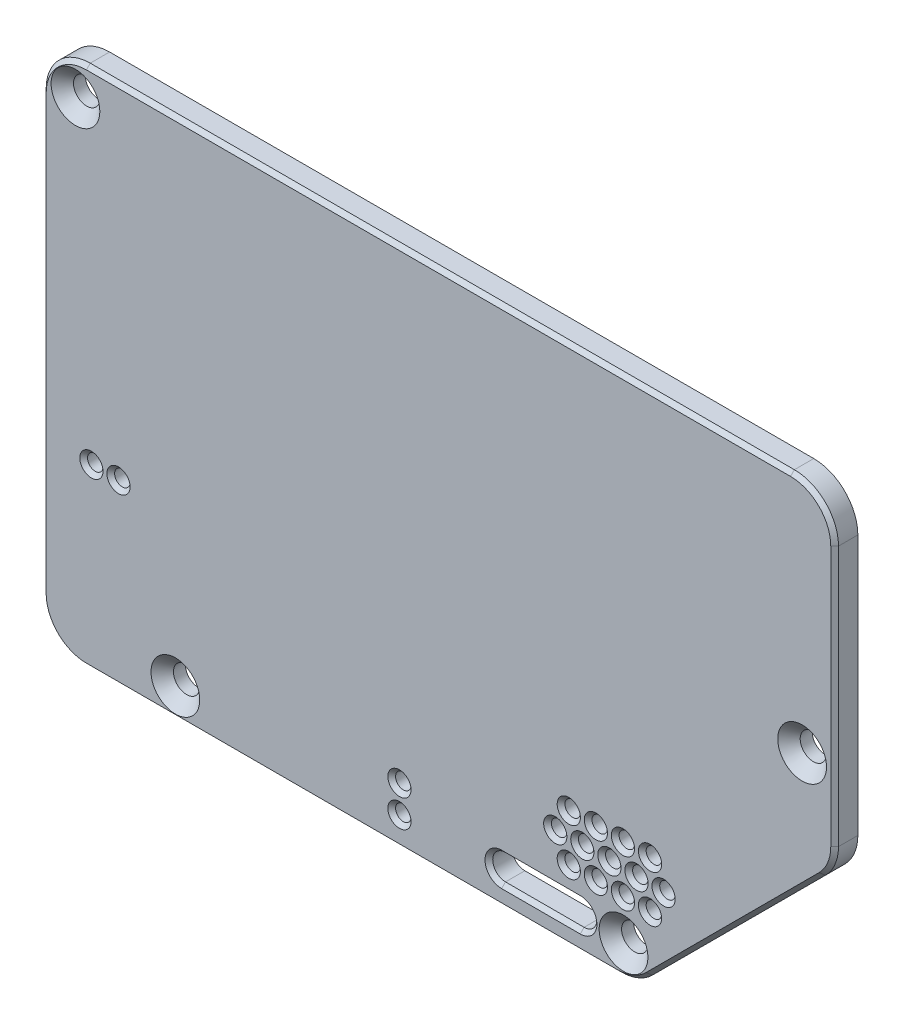
SolidWorks part; units mm, degrees
ref_plane "Front Plane" through (0, 0, 0) normal (0, 0, 1) x (1, 0, 0)
ref_plane "Top Plane" through (0, 0, 0) normal (0, 1, 0) x (1, 0, 0)
ref_plane "Right Plane" through (0, 0, 0) normal (1, 0, 0) x (0, 0, -1)
sketch "Sketch2" plane through (0, 0, 8.62) normal (0, 0, 1) x (1, 0, 0)
  line L0 (4.5, 66.2) -> (95.5, 66.2)
  line L1 (101.2, 60.5) -> (101.2, 26.864)
  line L2 (99.5305, 22.8335) -> (77.1665, 0.4695)
  line L3 (73.136, -1.2) -> (4.5, -1.2)
  line L4 (-1.2, 4.5) -> (-1.2, 60.5)
  line L5 (-1.5, 60.5) -> (-1.5, 4.5) construction
  arc A0 (4.5, -1.2) -> (-1.2, 4.5) centre (4.5, 4.5) cw
  arc A1 (77.1665, 0.4695) -> (73.136, -1.2) centre (73.136, 4.5) cw
  arc A2 (101.2, 26.864) -> (99.5305, 22.8335) centre (95.5, 26.864) cw
  arc A3 (95.5, 66.2) -> (101.2, 60.5) centre (95.5, 60.5) cw
  arc A4 (4.5, 66.2) -> (-1.2, 60.5) centre (4.5, 60.5) ccw
  arc A5 (-1.5, 4.5) -> (4.5, -1.5) centre (4.5, 4.5) ccw construction
  arc A6 (4.5, 66.5) -> (-1.5, 60.5) centre (4.5, 60.5) ccw construction
  arc A7 (101.5, 60.5) -> (95.5, 66.5) centre (95.5, 60.5) ccw construction
  arc A8 (73.136, -1.5) -> (77.3787, 0.2574) centre (73.136, 4.5) ccw construction
  circle A9 centre (3.0858, 61.9142) radius 1.5 construction
  circle A10 centre (16, 2.5) radius 1.5 construction
  circle A11 centre (73.9175, 2.659) radius 1.5 construction
  circle A12 centre (97, 35.5) radius 1.5 construction
  circle A13 centre (16, 2.5) radius 1.35 construction
  arc A14 (101.3205, 25.4074) -> (101.5, 26.864) centre (95.5, 26.864) ccw construction
  circle A15 centre (73.9175, 2.659) radius 1.35 construction
  circle A16 centre (97, 35.5) radius 1.35 construction
  circle A17 centre (3.0858, 61.9142) radius 1.35 construction
  dimension "D1" = 0.3
  dimension "D2" = 3
extrude "Boss-Extrude1" add sketch "Sketch2" along normal blind 3
hole_wizard "CSK for M3 Flat Head Machine Screw1" positions "Sketch4" profile "Sketch5" countersink size "M3" standard "ANSI Metric" end condition through all
sketch "Sketch4" plane through (0, 0, 11.62) normal (0, 0, 1) x (1, 0, 0)
  point P0 (3.0858, 61.9142)
  point P3 (16, 2.5)
  point P6 (73.9175, 2.659)
  point P9 (97, 35.5)
sketch "Sketch5" plane through (3.0858, 61.9142, 11.62) normal (1, 0, 0) x (0, -1, 0)
  line L0 (0, 0) -> (0, 3)
  line L1 (0, 3) -> (1.7, 3)
  line L2 (1.7, 3) -> (1.7, 1.45)
  line L3 (1.7, 1.45) -> (3.15, 0)
  line L5 (3.15, 0) -> (0, 0)
  line L6 (-1.7, 1.45) -> (-3.15, 0) construction
  line L11 (0, -6.35) -> (0, 107.95) construction
  dimension "Thru Hole Dia." = 3.4
  dimension "Thru Hole Depth" = 3
  dimension "Near C'Sink Dia." = 6.3
  dimension "Near C'Sink Angle" = 90
sketch "Sketch6" plane through (0, 0, 11.62) normal (0, 0, 1) x (1, 0, 0)
  line L6 (72.0938, 16.422) -> (72.0938, 14.1605) construction
  line L8 (78.5938, 16.422) -> (65.5938, 16.422) construction
  line L10 (68.326, 3.048) -> (58.166, 3.048) construction
  line L11 (68.326, 1.397) -> (58.166, 1.397)
  line L12 (68.326, 4.699) -> (58.166, 4.699)
  line L13 (72.0938, 7.6835) -> (72.0938, 5.422) construction
  line L14 (65.5938, 5.422) -> (78.5938, 5.422) construction
  arc A4 (68.326, 1.397) -> (68.326, 4.699) centre (68.326, 3.048) ccw
  arc A5 (58.166, 4.699) -> (58.166, 1.397) centre (58.166, 3.048) ccw
  point P26 (63.246, 3.048)
  dimension "D4" = 3.302
extrude "Cut-Extrude1" cut sketch "Sketch6" against normal through all
sketch "Sketch7" plane through (0, 0, 11.62) normal (0, 0, 1) x (1, 0, 0)
  line L1 (19.25, 57.135) -> (67.25, 57.135)
  line L2 (18.615, 56.5) -> (18.615, 20.1)
  line L3 (19.25, 19.465) -> (67.25, 19.465)
  line L4 (67.885, 56.5) -> (67.885, 20.1)
  arc A4 (67.25, 57.135) -> (67.885, 56.5) centre (67.25, 56.5) cw
  arc A5 (67.25, 19.465) -> (67.885, 20.1) centre (67.25, 20.1) ccw
  arc A6 (18.615, 20.1) -> (19.25, 19.465) centre (19.25, 20.1) ccw
  arc A7 (19.25, 57.135) -> (18.615, 56.5) centre (19.25, 56.5) ccw
  dimension "D2" = 0.635
split line "Split Line1" [suppressed]
sketch "Sketch8" plane through (0, 0, 11.62) normal (0, 0, 1) x (1, 0, 0)
  circle A0 centre (44.958, 2.54) radius 1
  circle A1 centre (44.958, 6.096) radius 1
  dimension "D1" = 2
extrude "Cut-Extrude2" cut sketch "Sketch8" against normal blind 10
sketch "Sketch9" plane through (0, 0, 11.62) normal (0, 0, 1) x (1, 0, 0)
  line L0 (65.0938, 10.922) -> (68.5938, 10.922) construction
  line L1 (68.5938, 10.922) -> (72.0938, 10.922) construction
  line L2 (72.0938, 10.922) -> (75.5938, 10.922) construction
  line L3 (75.5938, 10.922) -> (79.0938, 10.922) construction
  line L4 (66.8438, 13.9531) -> (66.8438, 7.8909) construction
  line L5 (65.0938, 10.922) -> (66.8438, 7.8909) construction
  line L6 (70.3438, 7.8909) -> (70.3438, 13.9531) construction
  line L7 (72.0938, 15.272) -> (72.0938, 6.572) construction
  line L8 (73.8438, 13.9531) -> (73.8438, 7.8909) construction
  line L9 (75.8938, 15.272) -> (68.2938, 15.272) construction
  line L10 (77.3438, 7.8909) -> (77.3438, 13.9531) construction
  line L11 (68.2938, 6.572) -> (75.8938, 6.572) construction
  circle A0 centre (65.0938, 10.922) radius 1
  circle A1 centre (68.5938, 10.922) radius 1
  circle A2 centre (72.0938, 10.922) radius 1
  circle A3 centre (75.5938, 10.922) radius 1
  circle A4 centre (79.0938, 10.922) radius 1
  circle A5 centre (66.8438, 13.9531) radius 1
  circle A6 centre (70.3438, 13.9531) radius 1
  circle A7 centre (73.8438, 13.9531) radius 1
  circle A8 centre (77.3438, 13.9531) radius 1
  circle A9 centre (66.8438, 7.8909) radius 1
  circle A10 centre (70.3438, 7.8909) radius 1
  circle A11 centre (73.8438, 7.8909) radius 1
  circle A12 centre (77.3438, 7.8909) radius 1
  circle A13 centre (44.958, 6.096) radius 1 construction
  point P18 (66.8438, 10.922)
  point P19 (70.3438, 10.922)
  point P20 (73.8438, 10.922)
  point P21 (77.3438, 10.922)
  dimension "D1" = 3.5
extrude "Cut-Extrude3" cut sketch "Sketch9" against normal blind 10
sketch "Sketch10" plane through (0, 0, 11.62) normal (0, 0, 1) x (1, 0, 0)
  line L0 (5.1479, 21.844) -> (8.6479, 21.844) construction
  line L1 (6.8979, 23.4191) -> (6.8979, 20.2689) construction
  line L2 (9.3459, 23.4191) -> (4.4498, 23.4191) construction
  line L3 (4.4498, 20.2689) -> (9.3459, 20.2689) construction
  circle A0 centre (5.1479, 21.844) radius 1
  circle A1 centre (8.6479, 21.844) radius 1
  circle A2 centre (44.958, 6.096) radius 1 construction
  point P12 (6.8979, 21.844)
  dimension "D1" = 3.5
extrude "Cut-Extrude4" cut sketch "Sketch10" against normal blind 10
chamfer "Chamfer1" distance 0.5 angle 45 31 edges at (78.3438, 7.8909, 11.62) (80.0938, 10.922, 11.62) (78.3438, 13.9531, 11.62) (76.5938, 10.922, 11.62) (74.8438, 7.8909, 11.62) (74.8438, 13.9531, 11.62) (73.0938, 10.922, 11.62) (71.3438, 7.8909, 11.62) (71.3438, 13.9531, 11.62) (45.958, 2.54, 11.62) (45.958, 6.096, 11.62) (67.8438, 7.8909, 11.62) (69.5938, 10.922, 11.62) (67.8438, 13.9531, 11.62) (66.0938, 10.922, 11.62) (63.246, 1.397, 11.62) (69.977, 3.048, 11.62) (56.515, 3.048, 11.62) (63.246, 4.699, 11.62) (101.2, 43.682, 11.62) (99.5305, 64.5305, 11.62) (100.7661, 24.6827, 11.62) (50, 66.2, 11.62) (88.3485, 11.6515, 11.62) (0.4695, 64.5305, 11.62) (75.3173, -0.7661, 11.62) (-1.2, 32.5, 11.62) (38.818, -1.2, 11.62) (0.4695, 0.4695, 11.62) (9.6479, 21.844, 11.62) (6.1479, 21.844, 11.62)
